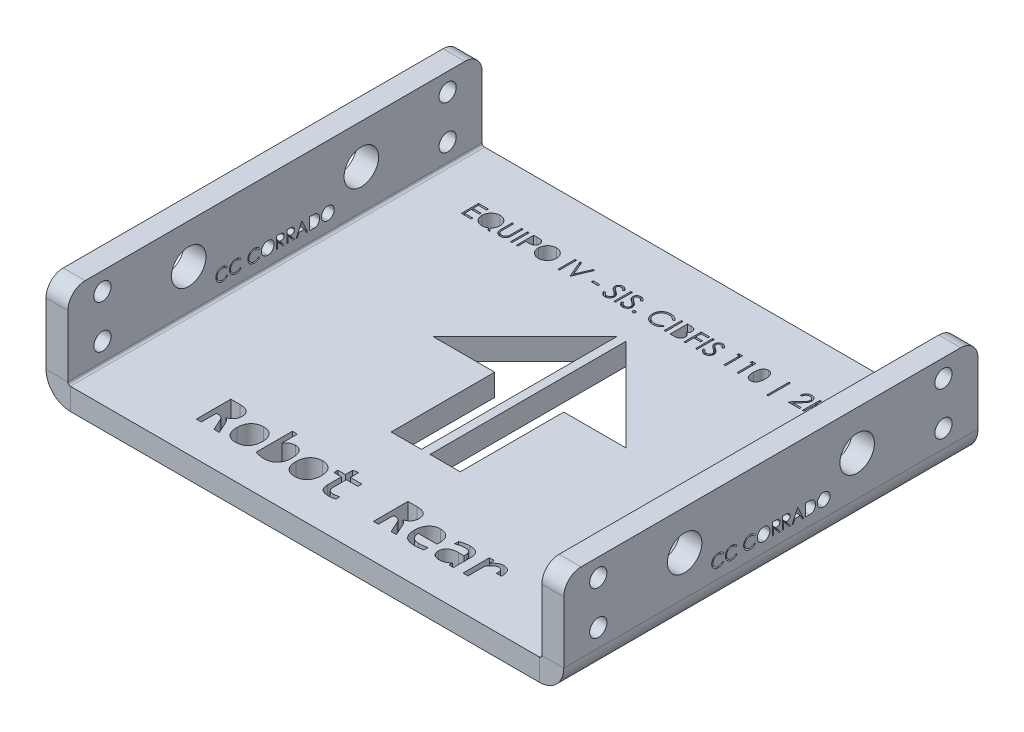
SolidWorks part; units mm, degrees
note: The reader was unsure of these and kept them because the rebuilt part matched: flange length of "Edge-Flange1".
ref_plane "Front Plane" through (0, 0, 0) normal (0, 0, 1) x (1, 0, 0)
ref_plane "Top Plane" through (0, 0, 0) normal (0, 1, 0) x (1, 0, 0)
ref_plane "Right Plane" through (0, 0, 0) normal (1, 0, 0) x (0, 0, -1)
sketch "Sketch1" plane through (0, 0, 0) normal (0, 1, 0) x (1, 0, 0)
  line L1 (-75, 60) -> (75, 60)
  line L2 (-75, 60) -> (-75, -60)
  line L3 (-75, -60) -> (75, -60)
  line L4 (75, 60) -> (75, -60)
  line L5 (-75, 60) -> (75, -60) construction
  line L6 (-75, -60) -> (75, 60) construction
  point P0 (0, 0)
  dimension "D1" = 150
  dimension "D2" = 120
base flange "Base-Flange1" sketch "Sketch1" thickness 6.35 reverse thickness direction no parameters "D1"=0.7366
edge flange "Edge-Flange1" sketch "Sketch10" flange profiles "Sketch10", "Sketch11" flange angle 90 flange length 30 flange position material inside bend radius 0.7366 thickness 6.35 parameters "D6"=10, "D8"=1
sketch "Sketch10" plane through (-75, 0, 0) normal (-1, 0, 0) x (0, 0, 1)
  line L2 (-60, 0) -> (-60, 23.65)
  line L3 (-60, 23.65) -> (60, 23.65)
  line L4 (60, 23.65) -> (60, 0)
  line L7 (-60, 0) -> (60, 0) construction
  line L8 (-60, 0) -> (60, 0)
sketch "Sketch11" plane through (75, 0, 0) normal (1, 0, 0) x (0, 0, -1)
  line L2 (60, 0) -> (60, 23.65)
  line L3 (60, 23.65) -> (-60, 23.65)
  line L4 (-60, 23.65) -> (-60, 0)
  line L5 (-60, 0) -> (60, 0) construction
  line L6 (-60, 0) -> (60, 0)
bend "EdgeBend1" bend radius 0.7366 bend angle 90 parameters "D5"=1
bend "EdgeBend2" bend radius 0.7366 bend angle 90 parameters "D5"=2
sketch "Sketch12" plane through (0, 0, 0) normal (1, 0, 0) x (0, 0, -1)
  line L0 (0, 23.65) -> (0, 0.7366) construction
  line L1 (60, 23.65) -> (-60, 23.65) construction
  line L2 (-60, 0.7366) -> (60, 0.7366) construction
  line L3 (0, 0.7366) -> (-60, 12.1933) construction
  line L4 (-60, 23.65) -> (-60, 0.7366) construction
  line L5 (-60, 12.1933) -> (0, 12.1933) construction
  line L6 (-50, 12.1933) -> (-50, 23.65) construction
  circle A0 centre (-50, 5.9433) radius 2.5
  circle A1 centre (-50, 18.4433) radius 2.5
  circle A2 centre (50, 5.9433) radius 2.5
  circle A3 centre (50, 18.4433) radius 2.5
  point P16 (-50, -7.7022)
  dimension "D2" = 5
  dimension "D1" = 50
  dimension "D3" = 12.5
extrude "Cut-Extrude1" cut sketch "Sketch12" against normal through all both and the other way through all
fillet "Fillet1" radius 5 4 edges at (-71.825, 23.65, 60) (-71.825, 23.65, -60) (71.825, 23.65, 60) (71.825, 23.65, -60)
sketch "Sketch13" plane through (0, 0, 0) normal (0, 1, 0) x (1, 0, 0)
  line L0 (-75, -50) -> (75, -50) construction
  line L1 (-75, -55) -> (-75, 55) construction
  line L2 (75, 55) -> (75, -55) construction
  line L3 (-67.9134, -60) -> (67.9134, -60) construction
  text T0 "Robot Rear" font "Consolas" height 10
  dimension "D1" = 10
extrude "Cut-Extrude2" cut sketch "Sketch13" against normal through all both
delete or keep bodies "Body-Delete/Keep 1" type delete bodies bodies 105 110 107 106 108 109 111
sketch "Sketch74" plane through (0, 0, 0) normal (1, 0, 0) x (0, 0, -1)
  circle A0 centre (25, 12.1933) radius 3.5 construction
  circle A1 centre (-25, 12.1933) radius 3.5 construction
  circle A2 centre (25, 12.1933) radius 3.5 construction
  circle A3 centre (-25, 12.1933) radius 3.5 construction
  circle A4 centre (-25, 12.1933) radius 4.5
  circle A5 centre (25, 12.1933) radius 4.5
  dimension "D1" = 1
sketch "Sketch82" plane through (0, 0, 0) normal (1, 0, 0) x (0, 0, -1)
  line L0 (-60, 3.65) -> (60, 3.65) construction
  line L1 (-60, 18.65) -> (-60, 0.7366) construction
  line L2 (60, 0.7366) -> (60, 18.65) construction
  line L3 (55, 23.65) -> (-55, 23.65) construction
  text T0 "CC CORRADO"
  dimension "D1" = 20
extrude "Cut-Extrude5" cut sketch "Sketch82" against normal through all both and the other way through all
delete or keep bodies "Body-Delete/Keep 3" type delete bodies bodies 140 145 146 147 142 138 137 144 143 148 141 139
sketch "Sketch109" plane through (0, 0, 0) normal (0, 1, 0) x (1, 0, 0)
  line L0 (-75, 40) -> (75, 40) construction
  line L1 (-75, -55) -> (-75, 55) construction
  line L2 (75, 55) -> (75, -55) construction
  line L3 (67.9134, 60) -> (-67.9134, 60) construction
  text T0 "EQUIPO IV - SIS. CIBFIS 110 | 2K22" font "Century Gothic" height 5
  dimension "D1" = 20
extrude "Cut-Extrude6" cut sketch "Sketch109" against normal through all
delete or keep bodies "Body-Delete/Keep 4" type delete bodies bodies 151 154 150 152 153 155
sketch "Sketch126" plane through (0, 0, 0) normal (1, 0, 0) x (0, 0, -1)
  circle A0 centre (25, 12.1933) radius 3.5 construction
  circle A1 centre (-25, 12.1933) radius 3.5 construction
  circle A4 centre (25, 12.1933) radius 3.5 construction
  circle A5 centre (-25, 12.1933) radius 3.5 construction
  circle A6 centre (-25, 12.1933) radius 5
  circle A7 centre (25, 12.1933) radius 5
  point P4 (0, 0)
  dimension "D1" = 1.5
extrude "Cut-Extrude7" cut sketch "Sketch126" against normal through all both and the other way through all
sketch "Sketch127" plane through (0, 0, 0) normal (0, 1, 0) x (1, 0, 0)
  line L0 (0, 60) -> (0, -60) construction
  line L1 (67.9134, 60) -> (-67.9134, 60) construction
  line L2 (-67.9134, -60) -> (67.9134, -60) construction
  line L3 (0, 33) -> (-28, 5)
  line L5 (-28, 5) -> (-10, 5)
  line L7 (-10, 5) -> (-10, -25)
  line L8 (-10, -25) -> (10, -25)
  line L9 (10, 5) -> (10, -25)
  line L10 (28, 5) -> (10, 5)
  line L11 (0, 33) -> (28, 5)
  point P12 (0, -25)
  dimension "D1" = 10
  dimension "D2" = 30
  dimension "D3" = 18
  dimension "D4" = 45
  dimension "D5" = 35
extrude "Cut-Extrude8" cut sketch "Sketch127" against normal through all both
sketch "Sketch129" plane through (0, 0, 0) normal (0, 1, 0) x (1, 0, 0)
  line L0 (0, 33) -> (0, -25)
  line L3 (-10, -25) -> (10, -25) construction
extrude "Extrude-Thin1" add sketch "Sketch129" against normal up to surface (6.35 mm away) thin up to face at (0, -6.35, -0.4286) thin type mid plane wall 2.5
sketch "Bend-Lines1" [suppressed] plane through (0, 0, 0) normal (0, 1, 0) x (1, 0, 0)
sketch "Bounding-Box1" [suppressed] plane through (0, 0, 0) normal (0, 1, 0) x (1, 0, 0)
sheet metal parameters "Sheet-Metal1" thickness 6.35 parameters "D1"=0.7366
flat pattern "Flat-Pattern1" [suppressed]
sketch "Bend-Lines2" plane through (0, 0, 0) normal (0, 1, 0) x (1, 0, 0)
sketch3d "Bounding-Box2" [suppressed]
  line L0 (-75, -60, 0) -> (75, -60, 0) construction
  line L1 (-75, 60, 0) -> (75, 60, 0) construction
  line L2 (-75, -60, 0) -> (-75, 60, 0) construction
  line L3 (75, -60, 0) -> (75, 60, 0) construction
sheet metal parameters "Sheet-Metal2" thickness 6.35 parameters "D1"=0.7366
flat pattern "Flat-Pattern1"
sketch "Bend-Lines2" plane through (0, 0, 0) normal (0, 1, 0) x (1, 0, 0)
  line L0 (70.9856, -60) -> (70.9856, 60) construction
  line L1 (-70.9856, 60) -> (-70.9856, -60) construction
  line L2 (70.9856, -60) -> (70.9856, 60) construction
  line L3 (-70.9856, 60) -> (-70.9856, -60) construction
sketch3d "Bounding-Box2" [suppressed]
  line L0 (91.9711, -60, 0) -> (-91.9711, -60, 0) construction
  line L1 (91.9711, 60, 0) -> (-91.9711, 60, 0) construction
  line L2 (91.9711, -60, 0) -> (91.9711, 60, 0) construction
  line L3 (-91.9711, -60, 0) -> (-91.9711, 60, 0) construction
bend of the flat pattern "Flatten-<EdgeBend1>1"
bend of the flat pattern "Flatten-<EdgeBend2>1"
sheet metal parameters "Sheet-Metal3" thickness 6.35 parameters "D1"=0.7366
flat pattern "Flat-Pattern1"
sketch "Bend-Lines2" plane through (0, 0, 0) normal (0, 1, 0) x (1, 0, 0)
  line L0 (70.9856, -60) -> (70.9856, 60) construction
  line L1 (-70.9856, 60) -> (-70.9856, -60) construction
  line L2 (70.9856, -60) -> (70.9856, 60) construction
  line L3 (-70.9856, 60) -> (-70.9856, -60) construction
sketch3d "Bounding-Box2" [suppressed]
  line L0 (-96.9711, -60, 0) -> (96.9711, -60, 0) construction
  line L1 (-96.9711, 60, 0) -> (96.9711, 60, 0) construction
  line L2 (-96.9711, -60, 0) -> (-96.9711, 60, 0) construction
  line L3 (96.9711, -60, 0) -> (96.9711, 60, 0) construction
bend of the flat pattern "Flatten-<EdgeBend1>1"
bend of the flat pattern "Flatten-<EdgeBend2>1"
sheet metal parameters "Sheet-Metal4" thickness 6.35 parameters "D1"=0.7366
flat pattern "Flat-Pattern4"
sketch "Bend-Lines3" plane through (0, 0, 0) normal (0, 1, 0) x (1, 0, 0)
  line L0 (70.9856, -60) -> (70.9856, 60) construction
  line L1 (-70.9856, 60) -> (-70.9856, -60) construction
  line L2 (70.9856, -60) -> (70.9856, 60) construction
  line L3 (-70.9856, 60) -> (-70.9856, -60) construction
sketch3d "Bounding-Box3" [suppressed]
  line L0 (-96.9711, -60, 0) -> (96.9711, -60, 0) construction
  line L1 (-96.9711, 60, 0) -> (96.9711, 60, 0) construction
  line L2 (-96.9711, -60, 0) -> (-96.9711, 60, 0) construction
  line L3 (96.9711, -60, 0) -> (96.9711, 60, 0) construction
bend of the flat pattern "Flatten-<EdgeBend2>2"
bend of the flat pattern "Flatten-<EdgeBend1>2"
sheet metal parameters "Sheet-Metal5" thickness 6.35 parameters "D1"=0.7366
flat pattern "Flat-Pattern5"
sketch "Bend-Lines4" plane through (0, 0, 0) normal (0, 1, 0) x (1, 0, 0)
sketch3d "Bounding-Box4" [suppressed]
  line L0 (-32.066, -43.3626, 0) -> (-31.9911, -49.0138, 0) construction
  line L1 (-27.7189, -43.305, 0) -> (-27.644, -48.9562, 0) construction
  line L2 (-32.066, -43.3626, 0) -> (-27.7189, -43.305, 0) construction
  line L3 (-31.9911, -49.0138, 0) -> (-27.644, -48.9562, 0) construction
sheet metal parameters "Sheet-Metal6" thickness 6.35 parameters "D1"=0.7366
flat pattern "Flat-Pattern6"
sketch "Bend-Lines5" plane through (0, 0, 0) normal (0, 1, 0) x (1, 0, 0)
sketch "Bounding-Box5" [suppressed] plane through (0, 0, 0) normal (0, 1, 0) x (1, 0, 0)
sheet metal parameters "Sheet-Metal7" thickness 6.35 parameters "D1"=0.7366
flat pattern "Flat-Pattern7"
sketch "Bend-Lines6" plane through (0, 0, 0) normal (0, 1, 0) x (1, 0, 0)
sketch3d "Bounding-Box6" [suppressed]
  line L0 (-23.0435, -43.3333, 0) -> (-23.0435, -49.1304, 0) construction
  line L1 (-19.2754, -43.3333, 0) -> (-19.2754, -49.1304, 0) construction
  line L2 (-23.0435, -43.3333, 0) -> (-19.2754, -43.3333, 0) construction
  line L3 (-23.0435, -49.1304, 0) -> (-19.2754, -49.1304, 0) construction
sheet metal parameters "Sheet-Metal8" thickness 6.35 parameters "D1"=0.7366
flat pattern "Flat-Pattern8"
sketch "Bend-Lines7" plane through (0, 0, 0) normal (0, 1, 0) x (1, 0, 0)
sketch3d "Bounding-Box7" [suppressed]
  line L0 (23.3363, -45.5072, 0) -> (19.4203, -45.5072, 0) construction
  line L1 (23.3363, -43.1884, 0) -> (19.4203, -43.1884, 0) construction
  line L2 (23.3363, -45.5072, 0) -> (23.3363, -43.1884, 0) construction
  line L3 (19.4203, -45.5072, 0) -> (19.4203, -43.1884, 0) construction
sheet metal parameters "Sheet-Metal9" thickness 6.35 parameters "D1"=0.7366
flat pattern "Flat-Pattern9"
sketch "Bend-Lines8" plane through (0, 0, 0) normal (0, 1, 0) x (1, 0, 0)
sketch3d "Bounding-Box8" [suppressed]
  line L0 (11.3043, -41.1594, 0) -> (11.3043, -44.4928, 0) construction
  line L1 (14.3478, -41.1594, 0) -> (14.3478, -44.4928, 0) construction
  line L2 (11.3043, -41.1594, 0) -> (14.3478, -41.1594, 0) construction
  line L3 (11.3043, -44.4928, 0) -> (14.3478, -44.4928, 0) construction
sheet metal parameters "Sheet-Metal10" thickness 6.35 parameters "D1"=0.7366
flat pattern "Flat-Pattern10"
sketch "Bend-Lines9" plane through (0, 0, 0) normal (0, 1, 0) x (1, 0, 0)
sketch "Bounding-Box9" [suppressed] plane through (0, 0, 0) normal (0, 1, 0) x (1, 0, 0)
sheet metal parameters "Sheet-Metal11" thickness 6.35 parameters "D1"=0.7366
flat pattern "Flat-Pattern11"
sketch "Bend-Lines10" plane through (0, 0, 0) normal (0, 1, 0) x (1, 0, 0)
sketch3d "Bounding-Box10" [suppressed]
  line L0 (31.5942, -48.9855, 0) -> (28.1159, -48.9855, 0) construction
  line L1 (31.5942, -46.5217, 0) -> (28.1159, -46.5217, 0) construction
  line L2 (31.5942, -48.9855, 0) -> (31.5942, -46.5217, 0) construction
  line L3 (28.1159, -48.9855, 0) -> (28.1159, -46.5217, 0) construction
sheet metal parameters "Sheet-Metal36" thickness 6.35 parameters "D1"=0.7366
flat pattern "Flat-Pattern36"
sketch "Bend-Lines35" plane through (0, 0, 0) normal (0, 1, 0) x (1, 0, 0)
  line L0 (70.9856, -60) -> (70.9856, 60) construction
  line L1 (-70.9856, 60) -> (-70.9856, -60) construction
  line L2 (70.9856, -60) -> (70.9856, 60) construction
  line L3 (-70.9856, 60) -> (-70.9856, -60) construction
sketch3d "Bounding-Box35" [suppressed]
  line L0 (-96.9711, -60, 0) -> (96.9711, -60, 0) construction
  line L1 (-96.9711, 60, 0) -> (96.9711, 60, 0) construction
  line L2 (-96.9711, -60, 0) -> (-96.9711, 60, 0) construction
  line L3 (96.9711, -60, 0) -> (96.9711, 60, 0) construction
bend of the flat pattern "Flatten-<EdgeBend2>5"
bend of the flat pattern "Flatten-<EdgeBend1>5"
sheet metal parameters "Sheet-Metal37" thickness 6.35 parameters "D1"=0.7366
flat pattern "Flat-Pattern37"
sketch "Bend-Lines36" plane through (0, 0, 0) normal (0, 1, 0) x (1, 0, 0)
sketch3d "Bounding-Box36" [suppressed]
  line L0 (-0.5536, 6.8487, 0) -> (-3.6033, 6.9113, 0) construction
  line L1 (-0.6144, 3.8884, 0) -> (-3.6641, 3.951, 0) construction
  line L2 (-0.5536, 6.8487, 0) -> (-0.6144, 3.8884, 0) construction
  line L3 (-3.6033, 6.9113, 0) -> (-3.6641, 3.951, 0) construction
sheet metal parameters "Sheet-Metal38" thickness 6.35 parameters "D1"=0.7366
flat pattern "Flat-Pattern38"
sketch "Bend-Lines37" plane through (0, 0, 0) normal (0, 1, 0) x (1, 0, 0)
sketch "Bounding-Box37" [suppressed] plane through (0, 0, 0) normal (0, 1, 0) x (1, 0, 0)
sheet metal parameters "Sheet-Metal39" thickness 6.35 parameters "D1"=0.7366
flat pattern "Flat-Pattern39"
sketch "Bend-Lines38" plane through (0, 0, 0) normal (0, 1, 0) x (1, 0, 0)
sketch "Bounding-Box38" [suppressed] plane through (0, 0, 0) normal (0, 1, 0) x (1, 0, 0)
sheet metal parameters "Sheet-Metal40" thickness 6.35 parameters "D1"=0.7366
flat pattern "Flat-Pattern40"
sketch "Bend-Lines39" plane through (0, 0, 0) normal (0, 1, 0) x (1, 0, 0)
sketch "Bounding-Box39" [suppressed] plane through (0, 0, 0) normal (0, 1, 0) x (1, 0, 0)
sheet metal parameters "Sheet-Metal41" thickness 6.35 parameters "D1"=0.7366
flat pattern "Flat-Pattern41"
sketch "Bend-Lines40" plane through (0, 0, 0) normal (0, 1, 0) x (1, 0, 0)
sketch3d "Bounding-Box40" [suppressed]
  line L0 (12.609, 4.009, 0) -> (12.609, 6.791, 0) construction
  line L1 (10.3654, 4.009, 0) -> (10.3654, 6.791, 0) construction
  line L2 (12.609, 4.009, 0) -> (10.3654, 4.009, 0) construction
  line L3 (12.609, 6.791, 0) -> (10.3654, 6.791, 0) construction
sheet metal parameters "Sheet-Metal42" thickness 6.35 parameters "D1"=0.7366
flat pattern "Flat-Pattern42"
sketch "Bend-Lines41" plane through (0, 0, 0) normal (0, 1, 0) x (1, 0, 0)
sketch "Bounding-Box41" [suppressed] plane through (0, 0, 0) normal (0, 1, 0) x (1, 0, 0)
sheet metal parameters "Sheet-Metal43" thickness 6.35 parameters "D1"=0.7366
flat pattern "Flat-Pattern43"
sketch "Bend-Lines42" plane through (0, 0, 0) normal (0, 1, 0) x (1, 0, 0)
sketch3d "Bounding-Box42" [suppressed]
  line L0 (3.7244, 6.791, 0) -> (5.2949, 6.791, 0) construction
  line L1 (3.7244, 5.6195, 0) -> (5.2949, 5.6195, 0) construction
  line L2 (3.7244, 6.791, 0) -> (3.7244, 5.6195, 0) construction
  line L3 (5.2949, 6.791, 0) -> (5.2949, 5.6195, 0) construction
sheet metal parameters "Sheet-Metal44" thickness 6.35 parameters "D1"=0.7366
flat pattern "Flat-Pattern44"
sketch "Bend-Lines43" plane through (0, 0, 0) normal (0, 1, 0) x (1, 0, 0)
sketch "Bounding-Box43" [suppressed] plane through (0, 0, 0) normal (0, 1, 0) x (1, 0, 0)
sheet metal parameters "Sheet-Metal45" thickness 6.35 parameters "D1"=0.7366
flat pattern "Flat-Pattern45"
sketch "Bend-Lines44" plane through (0, 0, 0) normal (0, 1, 0) x (1, 0, 0)
sketch "Bounding-Box44" [suppressed] plane through (0, 0, 0) normal (0, 1, 0) x (1, 0, 0)
sheet metal parameters "Sheet-Metal46" thickness 6.35 parameters "D1"=0.7366
flat pattern "Flat-Pattern46"
sketch "Bend-Lines45" plane through (0, 0, 0) normal (0, 1, 0) x (1, 0, 0)
sketch "Bounding-Box45" [suppressed] plane through (0, 0, 0) normal (0, 1, 0) x (1, 0, 0)
sheet metal parameters "Sheet-Metal47" thickness 6.35 parameters "D1"=0.7366
flat pattern "Flat-Pattern47"
sketch "Bend-Lines46" plane through (0, 0, 0) normal (0, 1, 0) x (1, 0, 0)
sketch3d "Bounding-Box46" [suppressed]
  line L0 (-8.3987, 5.1308, 0) -> (-8.3987, 6.4678, 0) construction
  line L1 (-7.1479, 5.1308, 0) -> (-7.1479, 6.4678, 0) construction
  line L2 (-8.3987, 5.1308, 0) -> (-7.1479, 5.1308, 0) construction
  line L3 (-8.3987, 6.4678, 0) -> (-7.1479, 6.4678, 0) construction
sheet metal parameters "Sheet-Metal48" thickness 6.35 parameters "D1"=0.7366
flat pattern "Flat-Pattern48"
sketch "Bend-Lines47" plane through (0, 0, 0) normal (0, 1, 0) x (1, 0, 0)
sketch "Bounding-Box47" [suppressed] plane through (0, 0, 0) normal (0, 1, 0) x (1, 0, 0)
sheet metal parameters "Sheet-Metal49" thickness 6.35 parameters "D1"=0.7366
flat pattern "Flat-Pattern49"
sketch "Bend-Lines48" plane through (0, 0, 0) normal (0, 1, 0) x (1, 0, 0)
  line L0 (70.9856, -60) -> (70.9856, 60) construction
  line L1 (-70.9856, 60) -> (-70.9856, -60) construction
  line L2 (70.9856, -60) -> (70.9856, 60) construction
  line L3 (-70.9856, 60) -> (-70.9856, -60) construction
sketch3d "Bounding-Box48" [suppressed]
  line L0 (-96.9711, -60, 0) -> (96.9711, -60, 0) construction
  line L1 (-96.9711, 60, 0) -> (96.9711, 60, 0) construction
  line L2 (-96.9711, -60, 0) -> (-96.9711, 60, 0) construction
  line L3 (96.9711, -60, 0) -> (96.9711, 60, 0) construction
bend of the flat pattern "Flatten-<EdgeBend2>6"
bend of the flat pattern "Flatten-<EdgeBend1>6"
sheet metal parameters "Sheet-Metal50" thickness 6.35 parameters "D1"=0.7366
flat pattern "Flat-Pattern50"
sketch "Bend-Lines49" plane through (0, 0, 0) normal (0, 1, 0) x (1, 0, 0)
sketch3d "Bounding-Box49" [suppressed]
  line L0 (-34.4561, 40.4198, 0) -> (-30.0985, 40.3502, 0) construction
  line L1 (-34.3885, 44.6495, 0) -> (-30.0309, 44.5799, 0) construction
  line L2 (-34.4561, 40.4198, 0) -> (-34.3885, 44.6495, 0) construction
  line L3 (-30.0985, 40.3502, 0) -> (-30.0309, 44.5799, 0) construction
sheet metal parameters "Sheet-Metal51" thickness 6.35 parameters "D1"=0.7366
flat pattern "Flat-Pattern51"
sketch "Bend-Lines50" plane through (0, 0, 0) normal (0, 1, 0) x (1, 0, 0)
sketch3d "Bounding-Box50" [suppressed]
  line L0 (-50.8476, 40.4705, 0) -> (-46.4938, 40.3042, 0) construction
  line L1 (-50.6862, 44.6969, 0) -> (-46.3324, 44.5306, 0) construction
  line L2 (-50.8476, 40.4705, 0) -> (-50.6862, 44.6969, 0) construction
  line L3 (-46.4938, 40.3042, 0) -> (-46.3324, 44.5306, 0) construction
sheet metal parameters "Sheet-Metal52" thickness 6.35 parameters "D1"=0.7366
flat pattern "Flat-Pattern52"
sketch "Bend-Lines51" plane through (0, 0, 0) normal (0, 1, 0) x (1, 0, 0)
sketch3d "Bounding-Box51" [suppressed]
  line L0 (27.9413, 44.611, 0) -> (27.9562, 40.3803, 0) construction
  line L1 (30.4413, 44.6198, 0) -> (30.4561, 40.3891, 0) construction
  line L2 (27.9413, 44.611, 0) -> (30.4413, 44.6198, 0) construction
  line L3 (27.9562, 40.3803, 0) -> (30.4561, 40.3891, 0) construction
sheet metal parameters "Sheet-Metal53" thickness 6.35 parameters "D1"=0.7366
flat pattern "Flat-Pattern53"
sketch "Bend-Lines52" plane through (0, 0, 0) normal (0, 1, 0) x (1, 0, 0)
sketch3d "Bounding-Box52" [suppressed]
  line L0 (8.3333, 40.5128, 0) -> (6.2821, 40.5128, 0) construction
  line L1 (8.3333, 42.3718, 0) -> (6.2821, 42.3718, 0) construction
  line L2 (8.3333, 40.5128, 0) -> (8.3333, 42.3718, 0) construction
  line L3 (6.2821, 40.5128, 0) -> (6.2821, 42.3718, 0) construction
sheet metal parameters "Sheet-Metal54" thickness 6.35 parameters "D1"=0.7366
flat pattern "Flat-Pattern54"
sketch "Bend-Lines53" plane through (0, 0, 0) normal (0, 1, 0) x (1, 0, 0)
sketch3d "Bounding-Box53" [suppressed]
  line L0 (-36.0897, 42.8095, 0) -> (-38.2692, 42.8095, 0) construction
  line L1 (-36.0897, 44.4872, 0) -> (-38.2692, 44.4872, 0) construction
  line L2 (-36.0897, 42.8095, 0) -> (-36.0897, 44.4872, 0) construction
  line L3 (-38.2692, 42.8095, 0) -> (-38.2692, 44.4872, 0) construction
sheet metal parameters "Sheet-Metal55" thickness 6.35 parameters "D1"=0.7366
flat pattern "Flat-Pattern55"
sketch "Bend-Lines54" plane through (0, 0, 0) normal (0, 1, 0) x (1, 0, 0)
sketch3d "Bounding-Box54" [suppressed]
  line L0 (7.9487, 42.8846, 0) -> (6.2821, 42.8846, 0) construction
  line L1 (7.9487, 44.4872, 0) -> (6.2821, 44.4872, 0) construction
  line L2 (7.9487, 42.8846, 0) -> (7.9487, 44.4872, 0) construction
  line L3 (6.2821, 42.8846, 0) -> (6.2821, 44.4872, 0) construction
sheet metal parameters "Sheet-Metal56" thickness 6.35 parameters "D1"=0.7366
flat pattern "Flat-Pattern49"
sketch "Bend-Lines48" plane through (0, 0, 0) normal (0, 1, 0) x (1, 0, 0)
  line L0 (70.9856, -60) -> (70.9856, 60) construction
  line L1 (-70.9856, 60) -> (-70.9856, -60) construction
  line L2 (70.9856, -60) -> (70.9856, 60) construction
  line L3 (-70.9856, 60) -> (-70.9856, -60) construction
sketch3d "Bounding-Box48" [suppressed]
  line L0 (-96.9711, -60, 0) -> (96.9711, -60, 0) construction
  line L1 (-96.9711, 60, 0) -> (96.9711, 60, 0) construction
  line L2 (-96.9711, -60, 0) -> (-96.9711, 60, 0) construction
  line L3 (96.9711, -60, 0) -> (96.9711, 60, 0) construction
bend of the flat pattern "Flatten-<EdgeBend2>6"
bend of the flat pattern "Flatten-<EdgeBend1>6"
sheet metal parameters "Sheet-Metal57" thickness 6.35 parameters "D1"=0.7366
flat pattern "Flat-Pattern49"
sketch "Bend-Lines48" plane through (0, 0, 0) normal (0, 1, 0) x (1, 0, 0)
  line L0 (70.9856, -60) -> (70.9856, 60) construction
  line L1 (-70.9856, 60) -> (-70.9856, -60) construction
  line L2 (70.9856, -60) -> (70.9856, 60) construction
  line L3 (-70.9856, 60) -> (-70.9856, -60) construction
sketch3d "Bounding-Box48" [suppressed]
  line L0 (-96.9711, -60, 0) -> (96.9711, -60, 0) construction
  line L1 (-96.9711, 60, 0) -> (96.9711, 60, 0) construction
  line L2 (-96.9711, -60, 0) -> (-96.9711, 60, 0) construction
  line L3 (96.9711, -60, 0) -> (96.9711, 60, 0) construction
bend of the flat pattern "Flatten-<EdgeBend2>6"
bend of the flat pattern "Flatten-<EdgeBend1>6"
sheet metal parameters "Sheet-Metal58" thickness 6.35 parameters "D1"=0.7366
flat pattern "Flat-Pattern49"
sketch "Bend-Lines48" plane through (0, 0, 0) normal (0, 1, 0) x (1, 0, 0)
  line L0 (70.9856, -60) -> (70.9856, 60) construction
  line L1 (-70.9856, 60) -> (-70.9856, -60) construction
  line L2 (70.9856, -60) -> (70.9856, 60) construction
  line L3 (-70.9856, 60) -> (-70.9856, -60) construction
sketch3d "Bounding-Box48" [suppressed]
  line L0 (-96.9711, -60, 0) -> (96.9711, -60, 0) construction
  line L1 (-96.9711, 60, 0) -> (96.9711, 60, 0) construction
  line L2 (-96.9711, -60, 0) -> (-96.9711, 60, 0) construction
  line L3 (96.9711, -60, 0) -> (96.9711, 60, 0) construction
bend of the flat pattern "Flatten-<EdgeBend2>6"
bend of the flat pattern "Flatten-<EdgeBend1>6"
